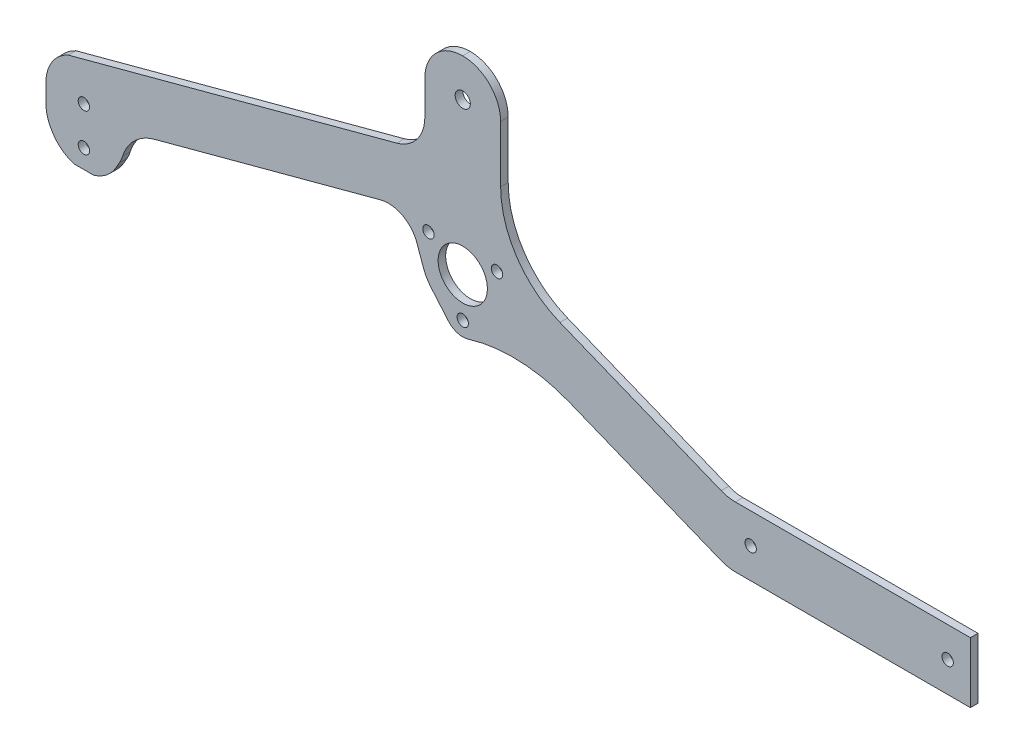
SolidWorks part; units mm, degrees
ref_plane "Спереди" through (0, 0, 0) normal (0, 0, 1) x (1, 0, 0)
ref_plane "Сверху" through (0, 0, 0) normal (0, 1, 0) x (1, 0, 0)
ref_plane "Справа" through (0, 0, 0) normal (1, 0, 0) x (0, 0, -1)
sketch "эскиз" plane through (0, 0, 0) normal (0, 0, 1) x (1, 0, 0)
  line L0 (110, -110) -> (110, -24) construction
  line L1 (-30, -110) -> (-30, -24) construction
  line L2 (-170, -24) -> (-136, -24) construction
  line L3 (-170, -110) -> (-30, -110) construction
  line L4 (-170, -24) -> (-188, -24) construction
  line L5 (-30, -110) -> (110, -110) construction
  line L6 (-170, -110) -> (-170, -24) construction
  line L7 (76, -24) -> (110, -24) construction
  line L8 (128, -24) -> (110, -24) construction
  line L9 (-42.5, -24) -> (-17.5, -24) construction
  line L10 (-170, -24) -> (-100, -24) construction
  line L11 (-100, -24) -> (-30, -24) construction
  line L12 (-100, -24) -> (0, 0) construction
  line L13 (0, 0) -> (110, -24) construction
  line L14 (-100, -24) -> (-100, -11) construction
  circle A0 centre (-170, -110) radius 57.5 construction
  circle A1 centre (-30, -110) radius 57.5 construction
  circle A2 centre (110, -110) radius 57.5 construction
  circle A3 centre (-188, -24) radius 1.5 construction
  circle A4 centre (-136, -24) radius 1.5 construction
  circle A5 centre (76, -24) radius 1.5 construction
  circle A6 centre (128, -24) radius 1.5 construction
  circle A7 centre (-42.5, -24) radius 1.5 construction
  circle A8 centre (-17.5, -24) radius 1.5 construction
  circle A9 centre (-100, -11) radius 1.5
  circle A10 centre (-100, -21) radius 1.5
  circle A11 centre (-100, -36) radius 2
  circle A12 centre (0, 40) radius 2
  point P31 (-153, -24)
  dimension "D1" = 115
  dimension "D4" = 3
  dimension "D7" = 25
  dimension "D12" = 3
  dimension "D11" = 4
  dimension "D17" = 4
  dimension "D2" = 140
  dimension "D3" = 86
  dimension "D5" = 18
  dimension "D6" = 34
  dimension "D8" = 70
  dimension "D9" = 280
  dimension "D10" = 30
  dimension "D13" = 10
  dimension "D14" = 12
  dimension "D15" = 110
  dimension "D16" = 15
  dimension "D18" = 40
sketch "эскиз 1" plane through (0, 0, 0) normal (0, 0, 1) x (1, 0, 0)
  line L0 (-194, -16) -> (-194, -32)
  line L1 (-194, -32) -> (-124, -32)
  line L2 (-124, -32) -> (-124, -47)
  line L3 (-194, -16) -> (-120, -16)
  line L5 (-11, -32) -> (-11, -16)
  line L6 (-124, -47) -> (-76, -47)
  line L9 (-109, -27) -> (-91, -27)
  line L10 (-76, -32) -> (-76, -47)
  line L11 (-30, -16) -> (-30, -42) construction
  line L12 (-76, -32) -> (-11, -32)
  line L13 (-11, -32) -> (-76, -32)
  line L15 (-80, -16) -> (-11, -16)
  line L16 (-100, -24) -> (-100, -11) construction
  line L17 (-30, -110) -> (-30, -24) construction
  line L18 (-170, -16) -> (-170, -32) construction
  line L19 (-170, -110) -> (-170, -24) construction
  line L20 (-170, -24) -> (-188, -24) construction
  line L21 (-100, -27) -> (-100, -47) construction
  line L22 (-109, -27) -> (-120, -16)
  line L23 (-91, -27) -> (-80, -16)
  circle A0 centre (-188, -24) radius 1.5
  circle A1 centre (-136, -24) radius 1.5
  circle A2 centre (-100, -36) radius 2
  circle A3 centre (-42.5, -24) radius 1.5
  circle A4 centre (-17.5, -24) radius 1.5
  circle A5 centre (-17.5, -24) radius 1.5 construction
  circle A6 centre (-42.5, -24) radius 1.5 construction
  circle A7 centre (-100, -36) radius 2 construction
  circle A8 centre (-136, -24) radius 1.5 construction
  circle A9 centre (-188, -24) radius 1.5 construction
  point P11 (-100, -27)
  point P25 (-100, -47)
  dimension "D1" = 24
  dimension "D2" = 19
  dimension "D3" = 16
  dimension "D4" = 11
  dimension "D5" = 45
  dimension "D7" = 70
  dimension "D8" = 8
  dimension "D9" = 3
extrude "тело маленькой арки" [suppressed] add sketch "эскиз 1" along normal blind 2
chamfer "Фаска1" [suppressed] distance 11 angle 45
sketch "Эскиз1" plane through (0, 0, 0) normal (0, 0, 1) x (1, 0, 0)
  line L0 (10, 8.208) -> (70, -16)
  line L1 (70, -16) -> (134, -16)
  line L2 (134, -16) -> (134, -32)
  line L3 (134, -32) -> (70, -32)
  line L4 (70, -32) -> (8.372, -7.1351)
  line L5 (-100, -24) -> (-30, -24) construction
  line L6 (-12.7222, 2.951) -> (-14.5644, 8.1359)
  line L7 (10, 8.208) -> (10, 50)
  line L8 (-104.0983, -1.8784) -> (-10, 23.3352)
  line L9 (76, -24) -> (110, -24) construction
  line L10 (-12.7222, 2.951) -> (-10.3652, -3.6828)
  line L11 (-90, -12.077) -> (-14.5644, 8.1359)
  line L12 (-8.9167, 9.5422) -> (-1.9932, 10.8179) construction
  line L13 (110, -110) -> (110, -24) construction
  line L14 (3.8054, -12.4932) -> (8.372, -7.1351)
  line L15 (-3.8054, -12.4932) -> (-8.372, -7.1351)
  line L16 (-110, -26) -> (-90, -26)
  line L18 (-100, -11) -> (-100, -26) construction
  line L19 (-100, -24) -> (-100, -11) construction
  line L20 (8.9167, 9.5422) -> (1.9932, 10.8179) construction
  line L21 (-90, -26) -> (-90, -12.077)
  line L22 (10, 50) -> (-10, 50)
  line L24 (-10, 50) -> (-10, 23.3352)
  line L27 (12.7222, 2.951) -> (10.3652, -3.6828) construction
  line L31 (-110, -11) -> (-110, -26)
  circle A0 centre (-100, -21) radius 1.5
  circle A1 centre (-100, -11) radius 1.5
  circle A2 centre (-100, -11) radius 1.5 construction
  circle A3 centre (-100, -21) radius 1.5 construction
  circle A4 centre (0, 0) radius 6.5
  circle A5 centre (0, 0) radius 11 construction
  arc A6 (-8.9167, 9.5422) -> (-12.7222, 2.951) centre (-8.0107, 4.625) ccw construction
  arc A7 (1.9932, 10.8179) -> (-1.9932, 10.8179) centre (0, 0) ccw construction
  arc A8 (-3.8054, -12.4932) -> (3.8054, -12.4932) centre (0, -9.25) ccw
  arc A9 (12.7222, 2.951) -> (8.9167, 9.5422) centre (8.0107, 4.625) ccw construction
  arc A10 (8.372, -7.1351) -> (10.3652, -3.6828) centre (0, 0) ccw construction
  arc A11 (-10.3652, -3.6828) -> (-8.372, -7.1351) centre (0, 0) ccw
  circle A12 centre (0, 0) radius 9.25 construction
  circle A13 centre (0, -10.45) radius 1.5
  circle A14 centre (-9.05, 5.225) radius 1.5
  circle A15 centre (9.05, 5.225) radius 1.5
  circle A16 centre (0, 0) radius 7.65 construction
  circle A17 centre (128, -24) radius 1.5
  circle A18 centre (76, -24) radius 1.5
  circle A19 centre (76, -24) radius 1.5 construction
  circle A20 centre (128, -24) radius 1.5 construction
  circle A21 centre (0, 40) radius 2
  circle A22 centre (0, 40) radius 2 construction
  arc A24 (-104.0983, -1.8784) -> (-110, -11) centre (-100, -11) ccw
  point P27 (134, -24)
  point P33 (0, 50)
  point P62 (0, 0)
  point P68 (0, 0)
  dimension "D2" = 13
  dimension "D3" = 3
  dimension "D5" = 5
  dimension "D6" = 18.5
  dimension "D7" = 22
  dimension "D14" = 3
  dimension "D17" = 15.3
  dimension "D20" = 20
  dimension "D13" = 13.5
  dimension "D4" = 15
  dimension "D1" = 16
  dimension "D8" = 10
  dimension "D9" = 6
  dimension "D10" = 24
  dimension "D12" = 74
  dimension "D15" = 3
  dimension "D19" = 10.45
  dimension "D21" = 5
extrude "тело большой арки" add sketch "Эскиз1" along normal blind 2
sketch "Эскиз2" plane through (0, 0, 2) normal (0, 0, 1) x (1, 0, 0)
  line L0 (-110, -18.6795) -> (-106.364, -24.9773)
  line L3 (-106.364, -24.9773) -> (-102.5472, -26)
  line L6 (-100, -36) -> (-100, -7.7157) construction
  line L12 (-110, -18.6795) -> (-110, -26)
  line L13 (-110, -11) -> (-110, -26) construction
  line L14 (-110, -26) -> (-90, -26) construction
  line L15 (-110, -26) -> (-102.5472, -26)
  line L19 (-90, -26) -> (-97.4528, -26)
  line L20 (-90, -18.6795) -> (-90, -26)
  line L21 (-93.636, -24.9773) -> (-97.4528, -26)
  line L22 (-90, -18.6795) -> (-93.636, -24.9773)
  line L23 (-100, -24) -> (-30, -24) construction
  circle A2 centre (-100, -36) radius 28.2843 construction
  circle A3 centre (-100, -36) radius 12.7279 construction
  dimension "D1" = 60
  dimension "D2" = 135
extrude "Упоры" cut sketch "Эскиз2" against normal up to next
fillet "Скругление5" radius 10 2 edges at (-106.364, -24.9773, 1) (-93.636, -24.9773, 1)
fillet "Скругление1" [suppressed] radius 10
fillet "Скругление2" [suppressed] radius 10
fillet "Скругление3" [suppressed] radius 15
fillet "Скругление4" [suppressed] radius 15
fillet "Скругление6" radius 12 1 edges at (-90, -12.077, 1)
fillet "Скругление7" radius 8 1 edges at (-14.5644, 8.1359, 1)
fillet "Скругление8" radius 40 1 edges at (8.372, -7.1351, 1)
fillet "Скругление9" radius 10 3 edges at (-10, 23.3352, 1) (10, 50, 1) (-10, 50, 1)
fillet "Скругление10" radius 25 1 edges at (10, 8.208, 1)
fillet "Скругление11" radius 10 4 edges at (-90, -18.6795, 1) (-110, -18.6795, 1) (70, -32, 1) (70, -16, 1)
